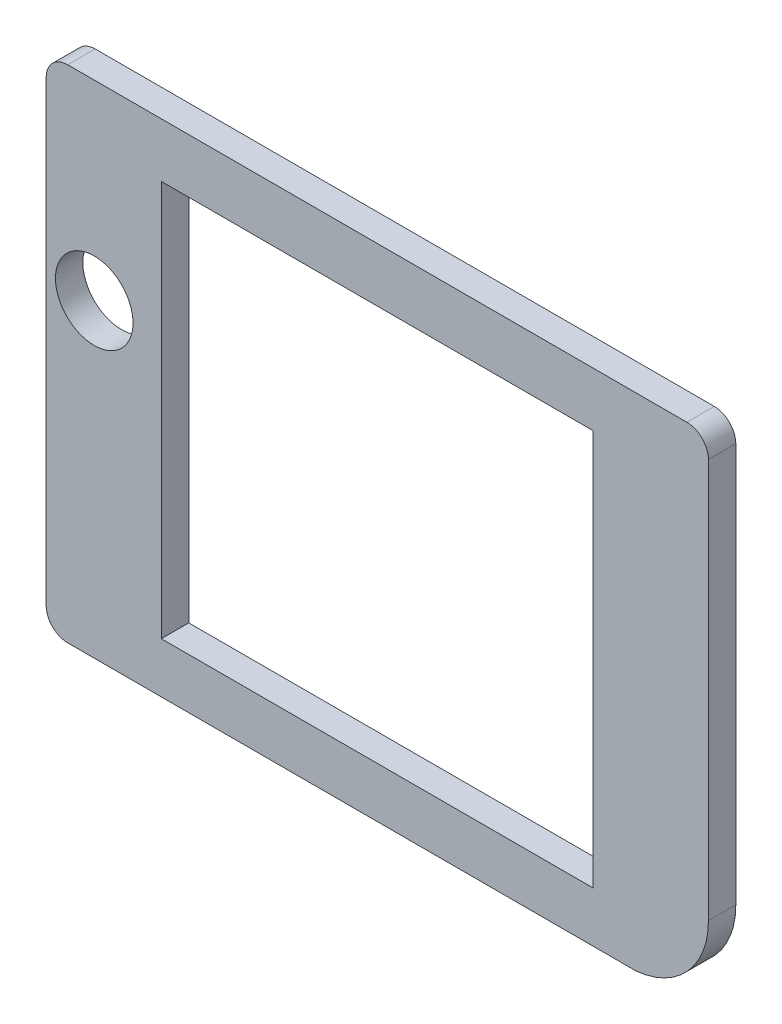
SolidWorks part; units mm, degrees
ref_plane "Front Plane" through (0, 0, 0) normal (0, 0, 1) x (1, 0, 0)
ref_plane "Top Plane" through (0, 0, 0) normal (0, 1, 0) x (1, 0, 0)
ref_plane "Right Plane" through (0, 0, 0) normal (1, 0, 0) x (0, 0, -1)
sketch "Sketch1" plane through (0, 0, 0) normal (0, 0, 1) x (1, 0, 0)
  line L0 (0.1058, 73.6301) -> (-0.0148, 62.4901) construction
  line L1 (-0.0148, 62.4901) -> (-0.0148, 56.2001) construction
  line L2 (-0.0148, 56.2001) -> (-0.0148, 10.268) construction
  line L3 (-15.4692, -49.8142) -> (-8.5409, -45.8142) construction
  line L4 (-15.4692, -49.8142) -> (0.5308, -49.8142) construction
  line L5 (0.5308, -49.8142) -> (7.4591, -45.8142) construction
  line L6 (-0.0148, 10.268) -> (0.1058, -73.6642) construction
  line L15 (-16.3293, -29.1587) -> (-16.3293, -23.8757)
  line L20 (-0.2968, -48.3429) -> (6.6759, -44.4208)
  line L21 (8.2583, -47.1985) -> (1.3584, -51.2855)
  line L22 (-44.5392, 73.6301) -> (44.7508, 73.6301)
  line L23 (44.7508, 73.6301) -> (44.7508, -73.6642)
  line L24 (44.7508, -73.6642) -> (-44.5392, -73.6642)
  line L25 (-44.5392, -73.6642) -> (-44.5392, 73.6301)
  line L26 (-25.0598, 56.2001) -> (-25.0598, 10.268)
  line L27 (-25.0598, 10.268) -> (25.0303, 10.268)
  line L28 (25.0303, 10.268) -> (25.0303, 56.2001)
  line L29 (25.0303, 56.2001) -> (-25.0598, 56.2001)
  line L34 (35.8896, 62.4901) -> (-35.9192, 62.4901)
  line L35 (-38.4192, 59.9901) -> (-38.4192, 6.918)
  line L36 (-35.9192, 4.418) -> (29.9974, 4.418)
  line L37 (38.3896, 13.668) -> (38.3896, 59.9901)
  line L38 (-16.2968, -48.3429) -> (-9.3241, -44.4208)
  line L39 (-7.7417, -47.1985) -> (-14.6416, -51.2855)
  line L150 (42.2525, -55.0539) -> (42.2511, -54.9499)
  circle A2 centre (-26.9008, -26.5172) radius 3.6
  arc A3 (8.2583, -47.1985) -> (6.6759, -44.4208) centre (7.4591, -45.8142) ccw
  arc A6 (-16.2968, -48.3429) -> (-14.6416, -51.2855) centre (-15.4692, -49.8142) ccw
  arc A7 (-7.7417, -47.1985) -> (-9.3241, -44.4208) centre (-8.5409, -45.8142) ccw
  circle A15 centre (18.9576, -29.5613) radius 3.5
  circle A16 centre (33.0683, -21.4917) radius 3.5
  arc A17 (-0.2968, -48.3429) -> (1.3584, -51.2855) centre (0.5308, -49.8142) ccw
  circle A19 centre (-32.8459, 40.326) radius 4.5
  arc A24 (38.3896, 59.9901) -> (35.8896, 62.4901) centre (35.8896, 59.9901) ccw
  arc A25 (-35.9192, 62.4901) -> (-38.4192, 59.9901) centre (-35.9192, 59.9901) ccw
  arc A26 (-38.4192, 6.918) -> (-35.9192, 4.418) centre (-35.9192, 6.918) ccw
  arc A27 (29.9974, 4.418) -> (38.3896, 13.668) centre (29.1397, 13.6282) ccw
  dimension "D4" = 11.14
  dimension "D8" = 7
  dimension "D11" = 9
  dimension "D12" = 7.2
  dimension "D14" = 9.25
  dimension "D15" = 2.5
  dimension "D2" = 89.29
  dimension "D3" = 147.2943
  dimension "D5" = 25.9097
  dimension "D6" = 8.0696
  dimension "D7" = 14.1107
  dimension "D9" = 7.7861
  dimension "D10" = 22.1641
  dimension "D13" = 10.5715
  dimension "D16" = 6.29
  dimension "D17" = 6.12
  dimension "D18" = 5.85
  dimension "D19" = 16
  dimension "D20" = 8
  dimension "D21" = 29.07
  dimension "D22" = 23.85
  dimension "D23" = 30
extrude "Bezel" add sketch "Sketch1" along normal blind 3.18 contours L36 A27 L37 A24 L34 A25 L35 A26 L29 L28 L27 L26 A19 region at (36.9765, 61.077, 0)
